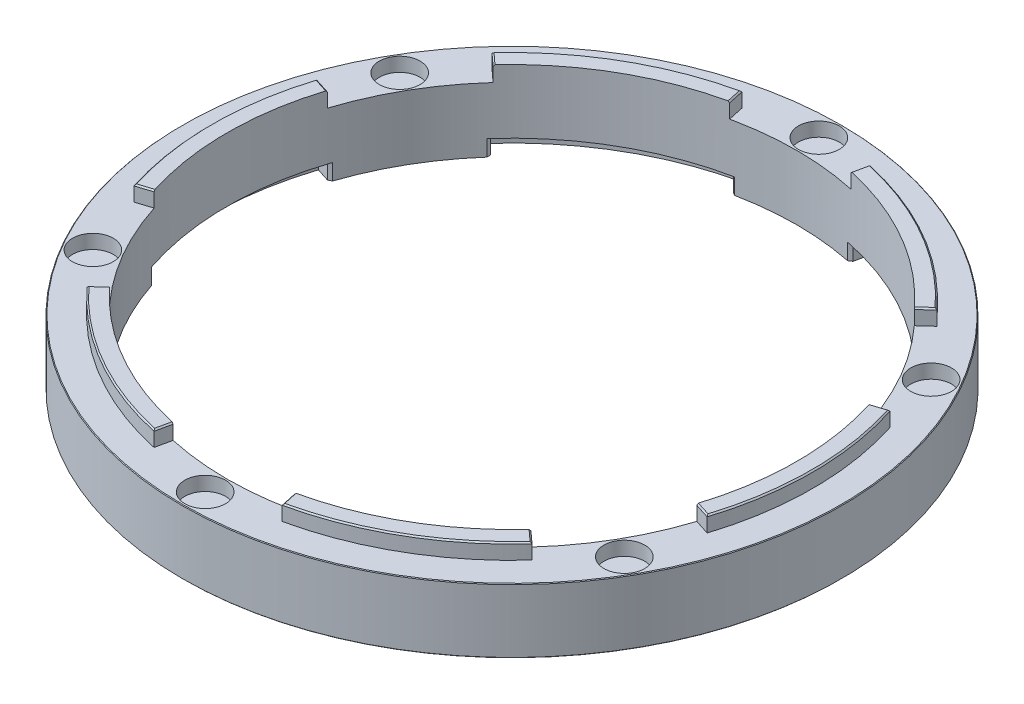
SolidWorks part; units mm, degrees
material "1060 合金"
ref_plane "前视基准面" through (0, 0, 0) normal (0, 0, 1) x (1, 0, 0)
ref_plane "上视基准面" through (0, 0, 0) normal (0, 1, 0) x (1, 0, 0)
ref_plane "右视基准面" through (0, 0, 0) normal (1, 0, 0) x (0, 0, -1)
sketch "草图1" plane through (0, 0, 0) normal (0, 0, 1) x (1, 0, 0)
  line L0 (0, 0) -> (-12.8351, 0) construction
  line L1 (-21.3, 0) -> (-21.3, -4.82)
  line L7 (-24.65, -4.82) -> (-21.3, -4.82)
  line L12 (0, 0.2665) -> (0, 12.2452) construction
  line L27 (-24.65, 0) -> (-21.3, 0)
  line L33 (-24.65, 0) -> (-24.65, -4.82)
  point P2 (-21.3416, 0)
  dimension "D1" = 42.6
  dimension "D4" = 4.82
  dimension "D6" = 3.35
revolve "旋转1" add sketch "草图1" angle 360 about L12
sketch "草图2" plane through (0, -4.82, 0) normal (0, -1, 0) x (1, 0, 0)
  line L0 (0, 0) -> (0, -50000) construction
  line L1 (0, 0) -> (43301.2702, 25000) construction
  line L2 (0, 0) -> (-43301.2702, 25000) construction
  line L3 (0, 21.3) -> (0, 24.6) construction
  line L4 (0, 0) -> (33.6187, 0) construction
  circle A0 centre (0, 0) radius 22.95 construction
  circle A1 centre (19.8753, 11.475) radius 1.525
  circle A2 centre (0, 0) radius 24.65
  circle A4 centre (19.8753, -11.475) radius 1.525
  circle A6 centre (-19.8753, -11.475) radius 1.525
  circle A7 centre (-19.8753, 11.475) radius 1.525
  circle A8 centre (0, 22.95) radius 1.525
  circle A9 centre (0, -22.95) radius 1.525
  circle A11 centre (0, 0) radius 24.65 construction
  point P10 (0, 0)
  point P15 (0, 22.95)
  dimension "D3" = 0
  dimension "D4" = 3.05
  dimension "D5" = 45.9
  dimension "D1" = 60
  dimension "D2" = 60
extrude "切除-拉伸1" cut sketch "草图2" against normal blind 1.05
sketch "草图3" plane through (0, -4.82, 0) normal (0, -1, 0) x (1, 0, 0)
  line L0 (0, 0) -> (0, 50000) construction
  line L1 (0, 0) -> (43301.2702, 25000) construction
  line L2 (0, 0) -> (43301.2702, -25000) construction
  line L3 (-16.7579, 15.0889) -> (-15.829, 14.2525)
  line L4 (-4.6884, 22.0572) -> (-4.4285, 20.8345)
  line L5 (4.6884, 22.0572) -> (4.4285, 20.8345)
  line L6 (16.7579, 15.0889) -> (15.829, 14.2525)
  line L7 (16.7579, -15.0889) -> (15.829, -14.2525)
  line L8 (4.6884, -22.0572) -> (4.4285, -20.8345)
  line L9 (21.4463, 6.9683) -> (20.2575, 6.5821)
  line L10 (21.4463, -6.9683) -> (20.2575, -6.5821)
  line L11 (-21.4463, -6.9683) -> (-20.2575, -6.5821)
  line L12 (-21.4463, 6.9683) -> (-20.2575, 6.5821)
  line L13 (-4.6884, -22.0572) -> (-4.4285, -20.8345)
  line L14 (-16.7579, -15.0889) -> (-15.829, -14.2525)
  line L15 (0, 0) -> (-4.4285, 20.8345) construction
  line L16 (0, 0) -> (-16.7579, 15.0889) construction
  line L17 (-2, -23.2) -> (2, -23.2)
  line L18 (-2, -23.2) -> (-2, -22.7)
  line L19 (-2, -22.7) -> (2, -22.7)
  line L20 (2, -23.2) -> (2, -22.7)
  line L21 (-2, -23.2) -> (2, -22.7) construction
  line L22 (-2, -22.7) -> (2, -23.2) construction
  circle A0 centre (0, 0) radius 21.3 construction
  circle A1 centre (0, 0) radius 21.3 construction
  arc A2 (-16.7579, 15.0889) -> (-4.6884, 22.0572) centre (0, 0) cw
  arc A3 (-15.829, 14.2525) -> (-4.4285, 20.8345) centre (0, 0) cw
  arc A4 (15.829, 14.2525) -> (4.4285, 20.8345) centre (0, 0) ccw
  arc A5 (16.7579, 15.0889) -> (4.6884, 22.0572) centre (0, 0) ccw
  arc A6 (4.4285, -20.8345) -> (15.829, -14.2525) centre (0, 0) ccw
  arc A7 (4.6884, -22.0572) -> (16.7579, -15.0889) centre (0, 0) ccw
  arc A8 (21.4463, 6.9683) -> (21.4463, -6.9683) centre (0, 0) cw
  arc A9 (20.2575, 6.5821) -> (20.2575, -6.5821) centre (0, 0) cw
  arc A10 (-20.2575, 6.5821) -> (-20.2575, -6.5821) centre (0, 0) ccw
  arc A11 (-21.4463, 6.9683) -> (-21.4463, -6.9683) centre (0, 0) ccw
  arc A12 (-4.6884, -22.0572) -> (-16.7579, -15.0889) centre (0, 0) cw
  arc A13 (-4.4285, -20.8345) -> (-15.829, -14.2525) centre (0, 0) cw
  circle A14 centre (0, 0) radius 21.3 construction
  point P5 (0, 0)
  point P17 (0, -22.95)
  dimension "D3" = 1.25
  dimension "D1" = 12
  dimension "12" = 12
  dimension "D4" = 4
  dimension "D5" = 0.5
extrude "切除-拉伸2" cut sketch "草图3" against normal blind 1.2
sketch "草图5" plane through (0, 0, 0) normal (0, 1, 0) x (-1, 0, 0)
  line L0 (0, 0) -> (0, 50000) construction
  line L1 (0.0003, 0.0002) -> (43303.3955, 24996.3188) construction
  line L2 (0, 0) -> (43301.2702, -25000) construction
  line L3 (-16.6417, 15.1428) -> (-15.7541, 14.3352)
  line L4 (-4.7932, 21.9835) -> (-4.5375, 20.8111)
  line L5 (4.7932, 21.9835) -> (4.5375, 20.8111)
  line L6 (16.6417, 15.1428) -> (15.7541, 14.3352)
  line L7 (16.6391, -15.1456) -> (15.7517, -14.3378)
  line L8 (4.7894, -21.9843) -> (4.534, -20.8118)
  line L9 (21.436, 6.8371) -> (20.2928, 6.4725)
  line L10 (21.4337, -6.8444) -> (20.2906, -6.4794)
  line L11 (-21.4337, -6.8444) -> (-20.2906, -6.4794)
  line L12 (-21.436, 6.8371) -> (-20.2928, 6.4725)
  line L13 (-4.7894, -21.9843) -> (-4.534, -20.8118)
  line L14 (-16.6391, -15.1456) -> (-15.7517, -14.3378)
  line L15 (0, 0) -> (-4.5375, 20.8111) construction
  line L16 (0, 0) -> (-16.6417, 15.1428) construction
  circle A0 centre (0, 0) radius 21.3 construction
  circle A1 centre (0, 0) radius 21.3 construction
  arc A2 (-16.6417, 15.1428) -> (-4.7932, 21.9835) centre (0, 0) cw
  arc A3 (-15.7541, 14.3352) -> (-4.5375, 20.8111) centre (0, 0) cw
  arc A4 (15.7541, 14.3352) -> (4.5375, 20.8111) centre (0, 0) ccw
  arc A5 (16.6417, 15.1428) -> (4.7932, 21.9835) centre (0, 0) ccw
  arc A6 (4.534, -20.8118) -> (15.7517, -14.3378) centre (0, 0) ccw
  arc A7 (4.7894, -21.9843) -> (16.6391, -15.1456) centre (0, 0) ccw
  arc A8 (21.436, 6.8371) -> (21.4337, -6.8444) centre (0, 0) cw
  arc A9 (20.2928, 6.4725) -> (20.2906, -6.4794) centre (0, 0) cw
  arc A10 (-20.2928, 6.4725) -> (-20.2906, -6.4794) centre (0, 0) ccw
  arc A11 (-21.436, 6.8371) -> (-21.4337, -6.8444) centre (0, 0) ccw
  arc A12 (-4.7894, -21.9843) -> (-16.6391, -15.1456) centre (0, 0) cw
  arc A13 (-4.534, -20.8118) -> (-15.7517, -14.3378) centre (0, 0) cw
  circle A15 centre (0, 0) radius 21.3 construction
  point P2 (0, 0)
  point P5 (0, 0)
  point P6 (0, 0)
  dimension "D3" = 1.2
  dimension "D1" = 12.3
  dimension "D2" = 60
  dimension "12" = 12.3
  dimension "D6" = 60.005
extrude "凸台-拉伸1" add sketch "草图5" along normal blind 1.15
chamfer "倒角1" distance 0.1 angle 45 18 edges at (20.8644, 1.15, 6.6548) (20.8622, 1.15, -6.6619) (16.1954, 1.15, -14.7417) (4.6617, 1.15, -21.3981) (-4.6617, 1.15, -21.3981) (-16.1954, 1.15, -14.7417) (-20.8622, 1.15, -6.6619) (-20.8644, 1.15, 6.6548) (-16.1979, 1.15, 14.739) (-4.6654, 1.15, 21.3973) (4.6654, 1.15, 21.3973) (16.1979, 1.15, 14.739) (22.5, 1.15, -0.0038) (11.2467, 1.15, -19.4875) (-11.2467, 1.15, -19.4875) (-22.5, 1.15, -0.0038) (-11.25, 1.15, 19.4856) (11.25, 1.15, 19.4856)
chamfer "倒角2" distance 0.05 angle 45 2 edges at (0, -4.82, -24.65) (0, 0, -24.65)
chamfer "倒角3" distance 0.2 angle 45 12 edges at (-15.829, -4.22, 14.2525) (-20.2575, -4.22, 6.5821) (-4.4285, -4.22, 20.8345) (4.4285, -4.22, 20.8345) (15.829, -4.22, 14.2525) (-15.829, -4.22, -14.2525) (-20.2575, -4.22, -6.5821) (-4.4285, -4.22, -20.8345) (4.4285, -4.22, -20.8345) (15.829, -4.22, -14.2525) (20.2575, -4.22, 6.5821) (20.2575, -4.22, -6.5821)
sketch "草图6" plane through (0, 0, 0) normal (0, 1, 0) x (-1, 0, 0)
  line L0 (0, 0) -> (0, -50000) construction
  line L1 (-3.5204, -2.0325) -> (43297.7497, 24997.9675) construction
  line L2 (-1.7602, 1.0163) -> (-43303.0304, 25001.0163) construction
  line L3 (0, 21.3) -> (0, 24.6) construction
  line L4 (0, 0) -> (33.6187, 0) construction
  circle A0 centre (0, 0) radius 22.95 construction
  circle A1 centre (19.8753, 11.475) radius 1.525
  circle A4 centre (19.8753, -11.475) radius 1.525
  circle A6 centre (-19.8753, -11.475) radius 1.525
  circle A7 centre (-19.8753, 11.475) radius 1.525
  circle A8 centre (0, 22.95) radius 1.525
  circle A9 centre (0, -22.95) radius 1.525
  point P2 (0, 0)
  point P10 (0, 0)
  point P15 (0, 22.95)
  dimension "D4" = 3.05
  dimension "D5" = 45.9
  dimension "D1" = 60
  dimension "D2" = 60
extrude "切除-拉伸3" cut sketch "草图6" against normal blind 1.05
